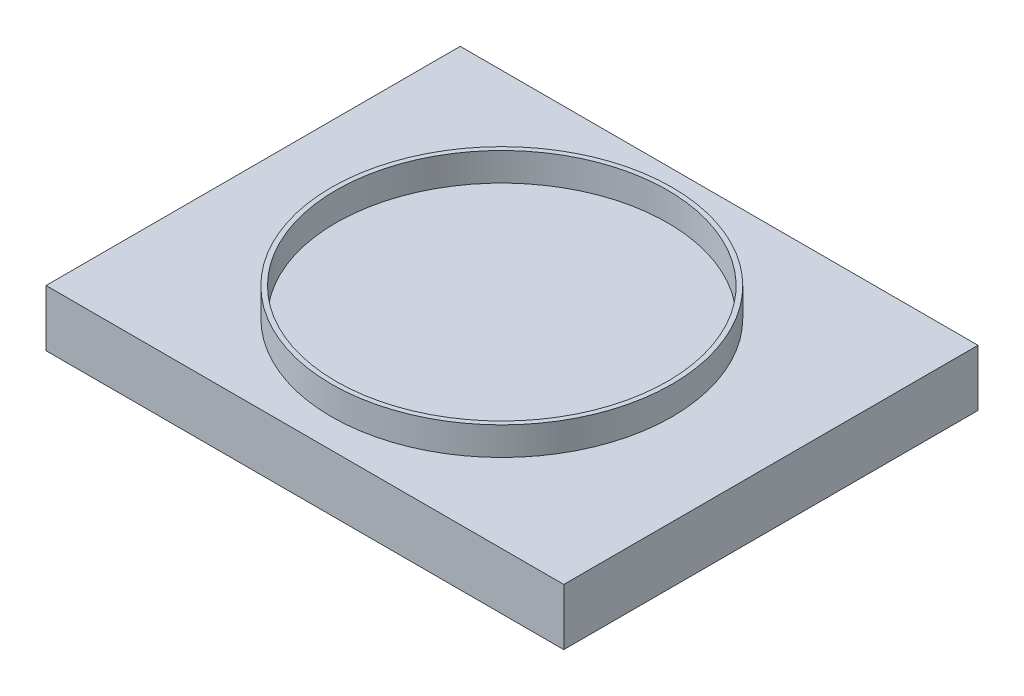
SolidWorks part; units mm, degrees
ref_plane "Front Plane" through (0, 0, 0) normal (0, 0, 1) x (1, 0, 0)
ref_plane "Top Plane" through (0, 0, 0) normal (0, 1, 0) x (1, 0, 0)
ref_plane "Right Plane" through (0, 0, 0) normal (1, 0, 0) x (0, 0, -1)
sketch "Sketch4" plane through (0, 0, 0) normal (0, 1, 0) x (1, 0, 0)
  line L0 (0, -46.7905) -> (24.3942, -46.7905) construction
  line L1 (0, -46.7905) -> (0, -24.9936) construction
  circle A0 centre (0, -46.7905) radius 17.6
  dimension "D1" = 35.2
extrude "Boss-Extrude3" add sketch "Sketch4" along normal blind 3 separate body
shell "Shell4" thickness 0.5 removed face at (0, 3, 64.3905) outward yes
ref_plane "Plane2" through (0, 0, 0) normal (0, 1, 0) x (1, 0, 0)
sketch "Sketch6" plane through (0, 0, 0) normal (0, 1, 0) x (1, 0, 0)
  line L1 (27.7675, -23.9741) -> (-27.2325, -23.9741)
  line L2 (27.7675, -23.9741) -> (27.7675, -67.9741)
  line L3 (27.7675, -67.9741) -> (-27.2325, -67.9741)
  line L4 (-27.2325, -23.9741) -> (-27.2325, -67.9741)
  dimension "D1" = 55
  dimension "D2" = 44
extrude "Boss-Extrude5" add sketch "Sketch6" against normal blind 6 contours L2 L1 L4 L3
sketch "Sketch7" plane through (0, -6, 0) normal (0, -1, 0) x (-1, 0, 0)
  line L1 (-26.3354, -25.4801) -> (25.919, -25.4801)
  line L2 (-26.3354, -25.4801) -> (-26.3354, -66.5709)
  line L3 (-26.3354, -66.5709) -> (25.919, -66.5709)
  line L4 (25.919, -25.4801) -> (25.919, -66.5709)
extrude "Cut-Extrude1" cut sketch "Sketch7" against normal blind 5
